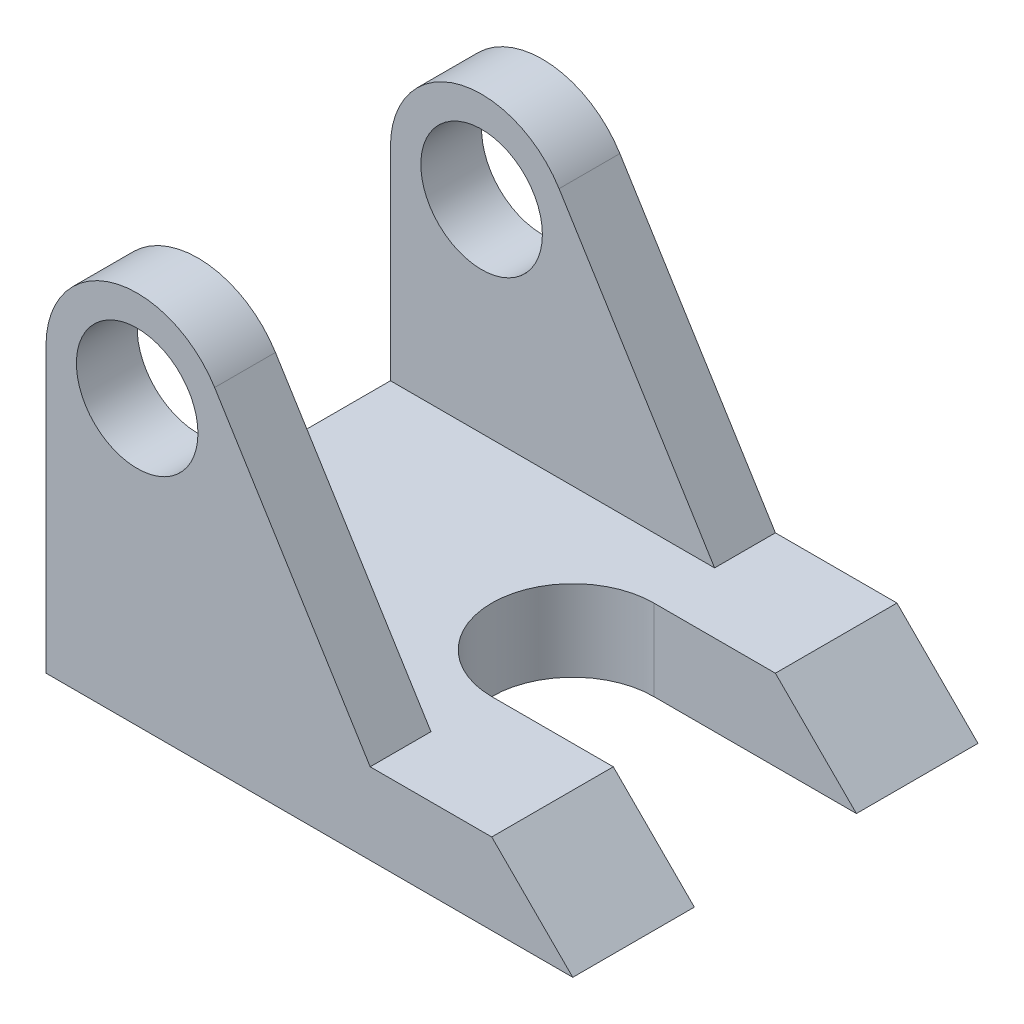
SolidWorks part; units mm, degrees
ref_plane "Front Plane" through (0, 0, 0) normal (0, 0, 1) x (1, 0, 0)
ref_plane "Top Plane" through (0, 0, 0) normal (0, 1, 0) x (1, 0, 0)
ref_plane "Right Plane" through (0, 0, 0) normal (1, 0, 0) x (0, 0, -1)
sketch "Sketch1" plane through (0, 0, 0) normal (0, 0, 1) x (1, 0, 0)
  line L0 (0, 0) -> (0, 20)
  line L1 (0, 20) -> (110, 20)
  line L2 (110, 20) -> (130, 0)
  line L3 (130, 0) -> (0, 0)
  point P3 (0, 0)
  dimension "D1" = 130
  dimension "D2" = 20
  dimension "D3" = 20
extrude "Boss-Extrude1" add sketch "Sketch1" along normal blind 50 and the other way blind 50
sketch "Sketch2" plane through (0, 20, 0) normal (0, 1, 0) x (1, 0, 0)
  line L0 (0, 0) -> (170.6971, 0) construction
  line L1 (130, 50) -> (130, -50) construction
  line L2 (80, 20) -> (130, 20)
  line L3 (80, -20) -> (130, -20)
  line L4 (110, 50) -> (110, -50) construction
  arc A0 (80, 20) -> (80, -20) centre (80, 0) ccw
  dimension "D1" = 40
  dimension "D2" = 50
  dimension "D3" = 30
extrude "Cut-Extrude1" cut sketch "Sketch2" against normal through all and the other way through all
sketch "Sketch3" plane through (0, 0, 50) normal (0, 0, 1) x (1, 0, 0)
  line L0 (0, 0) -> (0, 70)
  line L2 (41.6192, 81.862) -> (80, 20)
  line L3 (110, 20) -> (0, 20) construction
  arc A0 (41.6192, 81.862) -> (0, 70) centre (22.5, 70) ccw
  circle A1 centre (22.5, 70) radius 15
  point P9 (0, 0)
  line M7 (110, 20) -> (0, 20)
  dimension "D1" = 70
  dimension "D2" = 45
  dimension "D4" = 30
  dimension "D3" = 30
extrude "Boss-Extrude2" add sketch "Sketch3" against normal blind 100 contours L2 A0 L0 A1 M7 region at (32.6557, 46.1421, 50)
sketch "Sketch7" plane through (0, 0, 0) normal (0, 0, 1) x (1, 0, 0)
  line L0 (80, 20) -> (0, 20)
  line L1 (0, 70) -> (0, 0) construction
  line L2 (0, 20) -> (0, 70)
  line L3 (41.6192, 81.862) -> (80, 20)
  arc A1 (41.6192, 81.862) -> (0, 70) centre (22.5, 70) ccw
  point P12 (179.6973, 69.6954)
  point P13 (0, 0)
  point P15 (-52.117, 79.8669)
  point P16 (25.6718, 70)
  dimension "D2" = 45
  dimension "D1" = 70
  dimension "D3" = 50
extrude "Cut-Extrude2" cut sketch "Sketch7" against normal blind 35 and the other way blind 35
